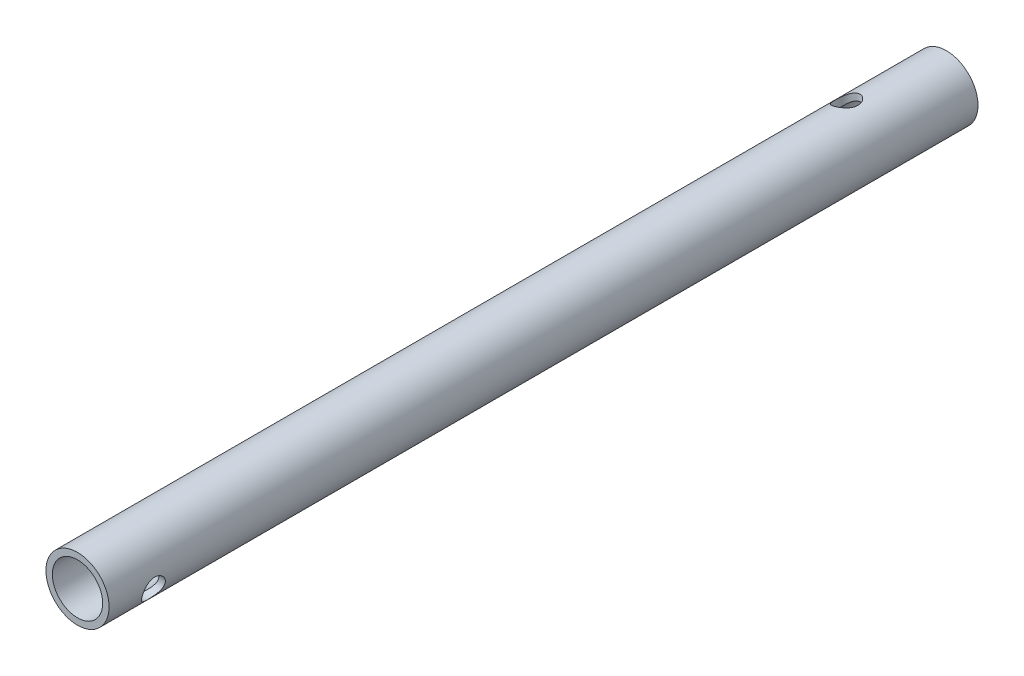
SolidWorks part; units mm, degrees
ref_plane "Front Plane" through (0, 0, 0) normal (0, 0, 1) x (1, 0, 0)
ref_plane "Top Plane" through (0, 0, 0) normal (0, 1, 0) x (1, 0, 0)
ref_plane "Right Plane" through (0, 0, 0) normal (1, 0, 0) x (0, 0, -1)
sketch "Sketch1" plane through (0, 0, 0) normal (0, 0, 1) x (1, 0, 0)
  circle A0 centre (0, 0) radius 17.526 construction
  circle A1 centre (0, 0) radius 13.97 construction
  point P3 (-17.526, 0)
  point P4 (17.526, 0)
  point P6 (-13.97, 0)
  point P7 (13.97, 0)
  dimension "OD" = 35.052
  dimension "Wall" = 3.556
  dimension "ID" = 27.94
sketch "Sketch2" plane through (0, 0, 0) normal (1, 0, 0) x (0, 0, -1)
  line L0 (241.3, 0) -> (-241.3, 0) construction
  line L2 (0, 17.526) -> (0, -17.526) construction
  line L3 (0, 17.526) -> (0, -17.526) construction
  line L4 (241.3, 17.526) -> (-241.3, 17.526) construction
  line L5 (241.3, -17.526) -> (-241.3, -17.526) construction
  line L6 (-241.3, -17.526) -> (-241.3, 17.526) construction
  line L7 (241.3, -17.526) -> (241.3, 17.526) construction
  line L8 (-206.248, -17.526) -> (-206.248, 17.526) construction
  line L9 (206.248, -17.526) -> (206.248, 17.526) construction
  point P3 (0, 0)
  point P9 (0, 17.526)
  point P11 (0, -17.526)
  point P13 (-241.3, 0)
  point P14 (241.3, 17.526)
  point P15 (-241.3, -17.526)
  point P16 (-241.3, 17.526)
  point P17 (-241.3, 0)
  point P18 (241.3, -17.526)
  point P19 (241.3, 0)
  point P22 (-206.248, 0)
  point P25 (206.248, 0)
  point P26 (-206.248, -17.526)
  point P27 (-206.248, 17.526)
  point P28 (206.248, 17.526)
  point P29 (206.248, -17.526)
  dimension "Length" = 482.6
  dimension "D1" = 35.052
sketch "Sketch3" plane through (0, 0, 0) normal (0, 0, 1) x (1, 0, 0)
  circle A0 centre (0, 0) radius 17.526 construction
  circle A1 centre (0, 0) radius 13.97 construction
  circle A2 centre (0, 0) radius 17.526
  circle A3 centre (0, 0) radius 13.97
extrude "Boss-Extrude1" add sketch "Sketch3" along normal mid plane 482.6
ref_plane "Plane1" through (0, 22.225, 0) normal (0, 1, 0) x (1, 0, 0)
sketch "Sketch4" plane through (0, 22.225, 0) normal (0, 1, 0) x (1, 0, 0)
  line L0 (13.97, 241.3) -> (-13.97, 241.3) construction
  line L1 (17.526, -241.3) -> (17.526, 241.3) construction
  circle A0 centre (-4.699, 190.5) radius 6.35
  dimension "D1" = 12.7
  dimension "D2" = 50.8
  dimension "D3" = 22.225
extrude "Cut-Extrude1" cut sketch "Sketch4" against normal through all
ref_plane "Plane2" through (22.225, 0, 0) normal (1, 0, 0) x (0, 0, -1)
sketch "Sketch5" plane through (22.225, 0, 0) normal (1, 0, 0) x (0, 0, -1)
  line L0 (186.2289, 17.526) -> (-241.3, 17.526) construction
  line L1 (-241.3, 17.526) -> (-241.3, -17.526) construction
  circle A0 centre (-215.9, -4.699) radius 6.35
  dimension "D1" = 12.7
  dimension "D2" = 22.225
  dimension "D3" = 25.4
extrude "Cut-Extrude2" cut sketch "Sketch5" against normal through all
equation "\"D1@Sketch2\"=\"OD@Sketch1\""
equation "\"D1@Boss-Extrude1\"=\"Length@Sketch2\""
equation "\"Wall@Sketch1\"=0.28/2"
